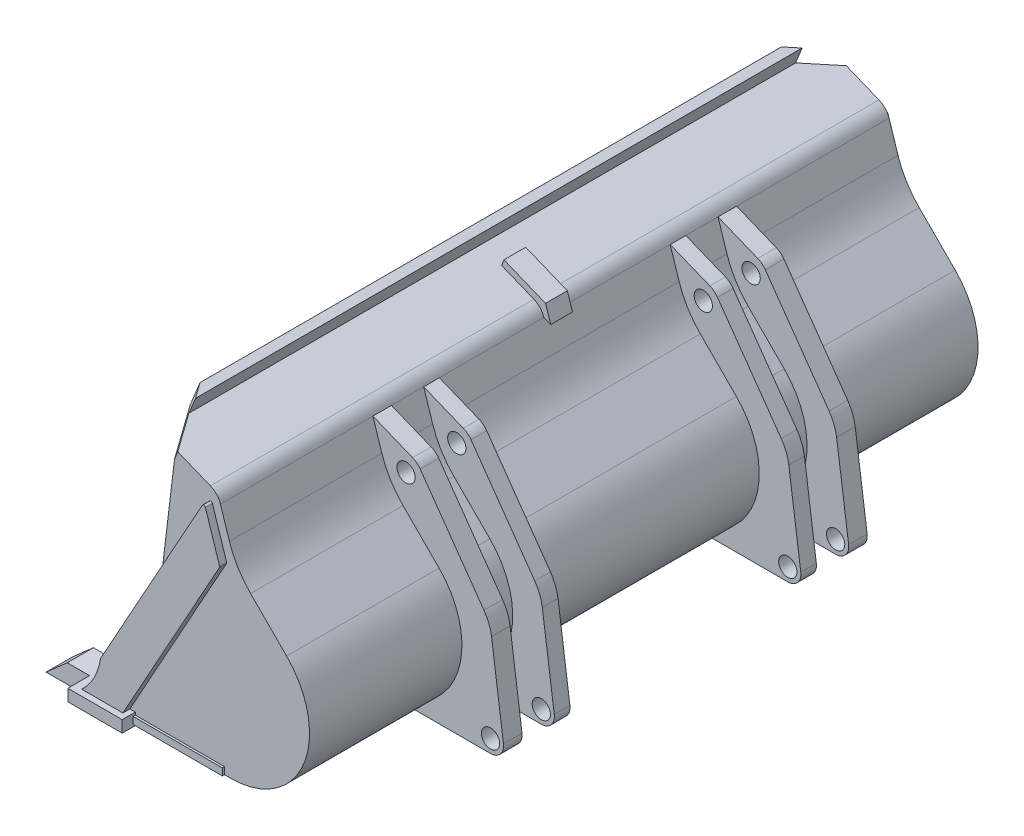
SolidWorks part; units mm, degrees
ref_plane "Front Plane" through (0, 0, 0) normal (0, 0, 1) x (1, 0, 0)
ref_plane "Top Plane" through (0, 0, 0) normal (0, 1, 0) x (1, 0, 0)
ref_plane "Right Plane" through (0, 0, 0) normal (1, 0, 0) x (0, 0, -1)
sketch "Sketch1" plane through (0, 0, 0) normal (0, 0, 1) x (1, 0, 0)
  line L0 (0, 0) -> (0, 1)
  line L1 (0, 1) -> (7.25, 16)
  line L2 (7.25, 16) -> (8.75, 28.5)
  line L3 (8.75, 28.5) -> (5.5533, 29.7974)
  line L4 (5.5533, 29.7974) -> (6.6814, 32.5772)
  line L5 (6.6814, 32.5772) -> (7.608, 32.2011)
  line L6 (7.608, 32.2011) -> (6.8559, 30.348)
  line L7 (6.8559, 30.348) -> (13.7401, 27.5539)
  line L8 (13.7401, 27.5539) -> (15.7923, 21.2039)
  line L9 (15.7923, 21.2039) -> (21.624, 15.3539)
  line L10 (15.25, 0) -> (0, 0)
  arc A0 (21.624, 15.3539) -> (15.25, 0) centre (15.25, 9) cw
  point P14 (10.1001, 20.1626)
  point P15 (15.3725, 19.0144)
  point P16 (17.6469, 8.4589)
  point P17 (21.7868, 10.2081)
  point P18 (18.8527, 11.7105)
  point P19 (8.1914, 30.1567)
  point P20 (17.3106, 18.3988)
  point P21 (9.0902, 29.4488)
  point P22 (0, 0)
  point P23 (0, 0)
  point P24 (14.6616, 21.5726)
  point P25 (21.4188, 15.5533)
  dimension "D12" = 9
  dimension "D1" = 1
  dimension "D2" = 16
  dimension "D3" = 28.5
  dimension "D4" = 8.75
  dimension "D5" = 7.25
  dimension "D6" = 3.45
  dimension "D7" = 1
  dimension "D8" = 1
  dimension "D9" = 2
  dimension "D10" = 153
  dimension "D11" = 15.25
  dimension "D13" = 5.85
  dimension "D14" = 130
  dimension "D15" = 6.35
extrude "Boss-Extrude1" add sketch "Sketch1" along normal blind 38.375
fillet "Fillet1" radius 10 1 edges at (15.7923, 21.2039, 19.1875)
fillet "Fillet2" radius 2 1 edges at (13.7401, 27.5539, 19.1875)
fillet "Fillet3" radius 5 1 edges at (7.25, 16, 19.1875)
shell "Shell1" thickness 1 removed face at (0, 0.5, 19.1875) removed face at (10.073, 19.817, 0) removed face at (3.4434, 8.1243, 19.1875) removed face at (7.1509, 16.029, 19.1875) removed face at (8.0497, 22.6643, 19.1875)
sketch "Sketch2" plane through (0, 0, 0) normal (0, 0, 1) x (1, 0, 0)
  line L0 (0, 0) -> (15.25, 0) construction
  line L1 (4.25, -0.25) -> (-2, -0.25)
  line L2 (4.25, -0.25) -> (4.25, 1.1)
  line L3 (4.25, 1.1) -> (-2, 1.1)
  line L4 (-2, -0.25) -> (-2, 1.1)
  line L5 (0, 1) -> (0, 0) construction
  point P5 (0, 0)
  dimension "D1" = 1.35
  dimension "D2" = 0.25
  dimension "D3" = 6.25
  dimension "D4" = 2
extrude "Boss-Extrude2" add sketch "Sketch2" along normal blind 39.875
sketch "Sketch3" plane through (0, 0, 39.875) normal (0, 0, 1) x (1, 0, 0)
  line L1 (4.25, 0) -> (14.5, 0)
  line L2 (4.25, 0) -> (4.25, 0.8)
  line L3 (4.25, 0.8) -> (14.5, 0.8)
  line L4 (14.5, 0) -> (14.5, 0.8)
  point P6 (6.9245, 1.4339)
  dimension "D1" = 10.25
  dimension "D2" = 0.8
extrude "Boss-Extrude3" add sketch "Sketch3" against normal up to surface (39.875 mm away) from offset 1.25 up to face at (10.8196, 15.7898, 0) offset against normal yes
sketch "Sketch4" plane through (0, 0, 38.375) normal (0, 0, 1) x (1, 0, 0)
  line L0 (-1.4, 0.8) -> (3.4593, 0.8)
  line L1 (3.4593, 0.8) -> (14.7517, 21.1721)
  line L2 (14.7517, 21.1721) -> (12.962, 26.7098)
  line L3 (12.962, 26.7098) -> (1.0667, 5.25)
  line L4 (-2, 1.1) -> (-2, -0.25) construction
  line L5 (4.25, 1.1) -> (-2, 1.1) construction
  line L6 (4.25, 0.8) -> (14.5, 0.8) construction
  line L8 (15.054, 23.4884) -> (14.0269, 26.6665) construction
  line L9 (-1.4, 0.8) -> (1.0667, 5.25) construction
  arc A0 (-1.4, 0.8) -> (1.0667, 5.25) centre (-6.1511, 6.3423) ccw
  dimension "D3" = 7.3
  dimension "D1" = 0.6
  dimension "D2" = 0.3
  dimension "D4" = 4.45
  dimension "D5" = 61
  dimension "D6" = 4.25
  dimension "D7" = 1
extrude "Boss-Extrude4" add sketch "Sketch4" along normal blind 0.8
fillet "Fillet4" radius 0.2 3 edges at (12.962, 26.7098, 38.775) (14.7517, 21.1721, 38.775) (-1.0709, 1.1, 38.775)
sketch "Sketch7" plane through (11.5446, 28.445, 0) normal (0.3761, 0.9266, 0) x (0.9266, -0.3761, 0)
  line L0 (-2.6101, -38.375) -> (-6.0601, -33.375)
  line L1 (-6.0601, -38.375) -> (-6.0601, 0) construction
  line L2 (-6.0601, -33.375) -> (-6.0601, -38.375)
  line L3 (-6.0601, -33.375) -> (-6.0601, -38.375)
  line L4 (-6.0601, -38.375) -> (-2.6101, -38.375)
  line M2 (-5.0601, -38.375) -> (1.4368, -38.375)
  line M5 (-5.0601, 0) -> (-5.0601, -38.375)
  dimension "D1" = 5
extrude "Cut-Extrude1" cut sketch "Sketch7" against normal blind 2 and the other way blind 10 contours L0 M2 M5 | L2 L4 L0 M5 region at (7.6126, 30.0408, 37.1914) region at (6.3664, 30.5466, 36.2168)
sketch "Sketch8" plane through (0, 0, 0) normal (0, 0, -1) x (-1, 0, 0)
  line L0 (-9.1696, 29.4089) -> (-9.4516, 30.1039)
  line L1 (-12.876, 27.9047) -> (-6.8559, 30.348) construction
  line L2 (-9.4516, 30.1039) -> (-14.2253, 28.1665)
  line L3 (-14.2253, 28.1665) -> (-15.568, 24.0118)
  line L5 (-15.054, 23.4884) -> (-14.0269, 26.6665) construction
  line L6 (-14.9495, 23.8119) -> (-14.0269, 26.6665)
  line L7 (-12.876, 27.9047) -> (-9.1696, 29.4089)
  line L9 (-15.568, 24.0118) -> (-14.9495, 23.8119)
  arc A3 (-14.0269, 26.6665) -> (-12.876, 27.9047) centre (-12.1238, 26.0515) cw
  dimension "D1" = 0.75
  dimension "D2" = 0.65
  dimension "D3" = 4
  dimension "D4" = 3
extrude "Boss-Extrude5" add sketch "Sketch8" against normal blind 1.25
mirror "Mirror1" about plane through (0, 0, 0) normal (0, 0, 1) of bodies 106
sketch "Sketch9" plane through (0, 0, -38.375) normal (0, 0, -1) x (-1, 0, 0)
  line L0 (-14.0269, 26.6665) -> (-15.054, 23.4884)
  line L1 (-17.4873, 19.5037) -> (-21.624, 15.3539)
  line L2 (-15.25, 0) -> (-14.5, 0)
  line L3 (-14.5, 0) -> (-4.25, 0)
  line L4 (-4.25, 0) -> (-4.25, -0.13)
  line L5 (-4.25, -0.13) -> (-27.5298, -0.13)
  line L6 (-29.0159, 1.5741) -> (-27.6464, 11.5427)
  line L7 (-26.7789, 13.7441) -> (-19.4615, 24.1185)
  line L8 (-18.5793, 24.8189) -> (-14.0269, 26.6665)
  line L9 (-12.876, 27.9047) -> (-9.1696, 29.4089) construction
  arc A0 (-15.054, 23.4884) -> (-17.4873, 19.5037) centre (-24.5695, 26.5636) cw
  arc A1 (-21.624, 15.3539) -> (-15.25, 0) centre (-15.25, 9) ccw
  arc A2 (-27.6464, 11.5427) -> (-26.7789, 13.7441) centre (-22.693, 10.8622) cw
  arc A3 (-27.5298, -0.13) -> (-29.0159, 1.5741) centre (-27.5298, 1.37) cw
  arc A4 (-19.4615, 24.1185) -> (-18.5793, 24.8189) centre (-17.8272, 22.9657) cw
  point P25 (-27.4807, 12.749)
  point P28 (-29.25, -0.13)
  point P31 (-19.1232, 24.5982)
  dimension "D6" = 5
  dimension "D7" = 1.5
  dimension "D8" = 2
  dimension "D1" = 5.5
  dimension "D2" = 14.5
  dimension "D3" = 13
  dimension "D4" = 25
  dimension "D5" = 0.13
sketch "Sketch10" plane through (0, 0, 0) normal (0, 0, 1) x (1, 0, 0)
  line L9 (4.25, 0) -> (4.25, -0.13)
  line L10 (4.25, -0.13) -> (27.5298, -0.13)
  line L11 (29.0159, 1.5741) -> (27.6464, 11.5427)
  line L12 (26.7789, 13.7441) -> (19.4615, 24.1185)
  line L13 (18.5793, 24.8189) -> (14.0269, 26.6665)
  line L14 (14.0269, 26.6665) -> (15.054, 23.4884)
  line L15 (17.4873, 19.5037) -> (21.624, 15.3539)
  line L16 (15.25, 0) -> (14.5, 0)
  line L17 (14.5, 0) -> (4.25, 0)
  line L18 (4.25, 0) -> (4.25, -0.13)
  line L19 (4.25, -0.13) -> (27.5298, -0.13)
  line L20 (29.0159, 1.5741) -> (27.6464, 11.5427)
  line L21 (26.7789, 13.7441) -> (19.4615, 24.1185)
  line L22 (18.5793, 24.8189) -> (14.0269, 26.6665)
  line L23 (14.0269, 26.6665) -> (15.054, 23.4884)
  line L24 (17.4873, 19.5037) -> (21.624, 15.3539)
  line L25 (15.25, 0) -> (14.5, 0)
  line L26 (14.5, 0) -> (4.25, 0)
  arc A5 (27.5298, -0.13) -> (29.0159, 1.5741) centre (27.5298, 1.37) ccw
  arc A6 (27.6464, 11.5427) -> (26.7789, 13.7441) centre (22.693, 10.8622) ccw
  arc A7 (19.4615, 24.1185) -> (18.5793, 24.8189) centre (17.8272, 22.9657) ccw
  arc A8 (15.054, 23.4884) -> (17.4873, 19.5037) centre (24.5695, 26.5636) ccw
  arc A9 (15.25, 0) -> (21.624, 15.3539) centre (15.25, 9) ccw
  arc A10 (27.5298, -0.13) -> (29.0159, 1.5741) centre (27.5298, 1.37) ccw
  arc A11 (27.6464, 11.5427) -> (26.7789, 13.7441) centre (22.693, 10.8622) ccw
  arc A12 (19.4615, 24.1185) -> (18.5793, 24.8189) centre (17.8272, 22.9657) ccw
  arc A13 (15.054, 23.4884) -> (17.4873, 19.5037) centre (24.5695, 26.5636) ccw
  arc A14 (15.25, 0) -> (21.624, 15.3539) centre (15.25, 9) ccw
  dimension "D1" = 0
extrude "Boss-Extrude6" add sketch "Sketch10" along normal mid plane 41.75
sketch "Sketch11" plane through (0, 0, 0) normal (0, 1, 0) x (1, 0, 0)
  line L0 (-18.5612, 0) -> (39.3342, 0) construction
  line L1 (40.088, 18.75) -> (15.25, 18.75)
  line L2 (0, 13.25) -> (40.088, 13.25)
  line L3 (0, 13.25) -> (0, -13.25)
  line L4 (0, -13.25) -> (40.088, -13.25)
  line L5 (40.088, 13.25) -> (40.088, -13.25)
  line L6 (0, 13.25) -> (40.088, -13.25) construction
  line L7 (0, -13.25) -> (40.088, 13.25) construction
  line L8 (40.088, -15.05) -> (15.25, -15.05)
  line L9 (40.088, -15.05) -> (40.088, -18.75)
  line L10 (40.088, -18.75) -> (15.25, -18.75)
  line L11 (15.25, -15.05) -> (15.25, -18.75) construction
  line L12 (40.088, -15.05) -> (15.25, -18.75) construction
  line L13 (40.088, -18.75) -> (15.25, -15.05) construction
  line L14 (15.25, 15.05) -> (15.25, 18.75) construction
  line L15 (40.088, 15.05) -> (15.25, 15.05)
  line L16 (40.088, 15.05) -> (40.088, 18.75)
  line L17 (40.088, 18.75) -> (15.25, 15.05) construction
  line L18 (40.088, 15.05) -> (15.25, 18.75) construction
  line L19 (15.25, 20.875) -> (15.25, 38.375) construction
  line L20 (15.25, 18.75) -> (15.25, 15.05)
  line L21 (15.25, -15.05) -> (15.25, -18.75)
  arc A0 (15.25, 18.75) -> (15.25, 15.05) centre (15.25, 16.9) ccw
  arc A1 (15.25, -15.05) -> (15.25, -18.75) centre (15.25, -16.9) ccw
  point P7 (20.044, 0)
  point P13 (27.669, -16.9)
  point P17 (27.669, 16.9)
  dimension "D4" = 0
  dimension "D1" = 26.5
  dimension "D2" = 30.1
  dimension "D3" = 37.5
sketch "Sketch12" plane through (0, 0, 20.875) normal (0, 0, 1) x (1, 0, 0)
  line L0 (15.25, 0) -> (15.25, -0.13)
  line L8 (15.25, 0) -> (4.25, 0)
  line L9 (4.25, 0) -> (4.25, -0.13)
  line L10 (4.25, -0.13) -> (27.5298, -0.13)
  line L11 (29.0159, 1.5741) -> (27.6464, 11.5427)
  line L12 (26.7789, 13.7441) -> (19.4615, 24.1185)
  line L13 (18.5793, 24.8189) -> (14.0269, 26.6665)
  line L14 (14.0269, 26.6665) -> (15.054, 23.4884)
  line L15 (17.4873, 19.5037) -> (21.624, 15.3539)
  line L18 (15.25, -0.13) -> (27.5298, -0.13)
  line L19 (29.0159, 1.5741) -> (27.6464, 11.5427)
  line L20 (26.7789, 13.7441) -> (19.4615, 24.1185)
  line L21 (18.5793, 24.8189) -> (14.0269, 26.6665)
  line L22 (14.0269, 26.6665) -> (15.054, 23.4884)
  line L23 (17.4873, 19.5037) -> (21.624, 15.3539)
  arc A5 (27.5298, -0.13) -> (29.0159, 1.5741) centre (27.5298, 1.37) ccw
  arc A6 (27.6464, 11.5427) -> (26.7789, 13.7441) centre (22.693, 10.8622) ccw
  arc A7 (19.4615, 24.1185) -> (18.5793, 24.8189) centre (17.8272, 22.9657) ccw
  arc A8 (15.054, 23.4884) -> (17.4873, 19.5037) centre (24.5695, 26.5636) ccw
  arc A9 (15.25, 0) -> (21.624, 15.3539) centre (15.25, 9) ccw
  arc A10 (27.5298, -0.13) -> (29.0159, 1.5741) centre (27.5298, 1.37) ccw
  arc A11 (27.6464, 11.5427) -> (26.7789, 13.7441) centre (22.693, 10.8622) ccw
  arc A12 (19.4615, 24.1185) -> (18.5793, 24.8189) centre (17.8272, 22.9657) ccw
  arc A13 (15.054, 23.4884) -> (17.4873, 19.5037) centre (24.5695, 26.5636) ccw
  arc A14 (15.25, 0) -> (21.624, 15.3539) centre (15.25, 9) ccw
  dimension "D1" = 0
extrude "Cut-Extrude2" cut sketch "Sketch12" against normal blind 3.7 from offset 2.13 offset against normal yes
extrude "Cut-Extrude5" cut sketch "Sketch11" against normal blind 0.25 contours L4 L5 L2 L3
extrude "Cut-Extrude6" cut sketch "Sketch12<2>" against normal blind 26.5 from offset 7.63 contours L18 A10 L19 A11 L20 A12 L21 L22 A13 L23 A14 L0 offset against normal yes
sketch "Sketch12<2>" plane through (0, 0, 20.875) normal (0, 0, 1) x (1, 0, 0) same geometry as "Sketch12"
sketch "Sketch13" plane through (0, -0.13, 0) normal (0, -1, 0) x (1, 0, 0)
  line L2 (15.25, 15.045) -> (15.25, 18.745) construction
  line L5 (15.25, 18.745) -> (15.25, 15.045)
  arc A1 (15.25, 18.745) -> (15.25, 15.045) centre (15.25, 16.895) ccw
extrude "Cut-Extrude8" cut sketch "Sketch13" against normal blind 0.13
mirror "Mirror2" about plane through (0, 0, 0) normal (0, 0, 1) of "Cut-Extrude8", "Cut-Extrude2"
sketch "Sketch14" plane through (0, 0, 20.875) normal (0, 0, 1) x (1, 0, 0)
  circle A0 centre (27.5298, 1.37) radius 1.05
  circle A1 centre (17.8272, 22.9657) radius 1.05
  dimension "D1" = 2.1
  dimension "D2" = 2.1
extrude "Cut-Extrude9" cut sketch "Sketch14" against normal through all both and the other way through all
sketch "Sketch15" plane through (0, 0, 39.875) normal (0, 0, 1) x (1, 0, 0)
  line L0 (4.25, 1.1) -> (3.75, -0.25)
  line L1 (-2, -0.25) -> (4.25, -0.25) construction
  line L2 (3.75, -0.25) -> (3.75, -1.05)
  line L3 (3.75, -1.05) -> (-7, -1.05)
  line L4 (-7, -1.05) -> (-4.5628, 1.1)
  line L5 (-4.5628, 1.1) -> (4.25, 1.1)
  line L6 (-2, 1.1) -> (-2, -0.25) construction
  line L8 (3.75, -0.25) -> (1.8953, -0.25) construction
  line L9 (4.25, -0.25) -> (4.25, 1.1) construction
  point P10 (-4.398, 0.8973)
  dimension "D1" = 3.25
  dimension "D2" = 5
  dimension "D3" = 0.8
  dimension "D5" = 0.5
extrude "Boss-Extrude7" add sketch "Sketch15" against normal blind 3 from offset 2.5 offset against normal yes
pattern_linear "LPattern1" count 7 spacing 12 along (0, 0, -1) of "Boss-Extrude7"
